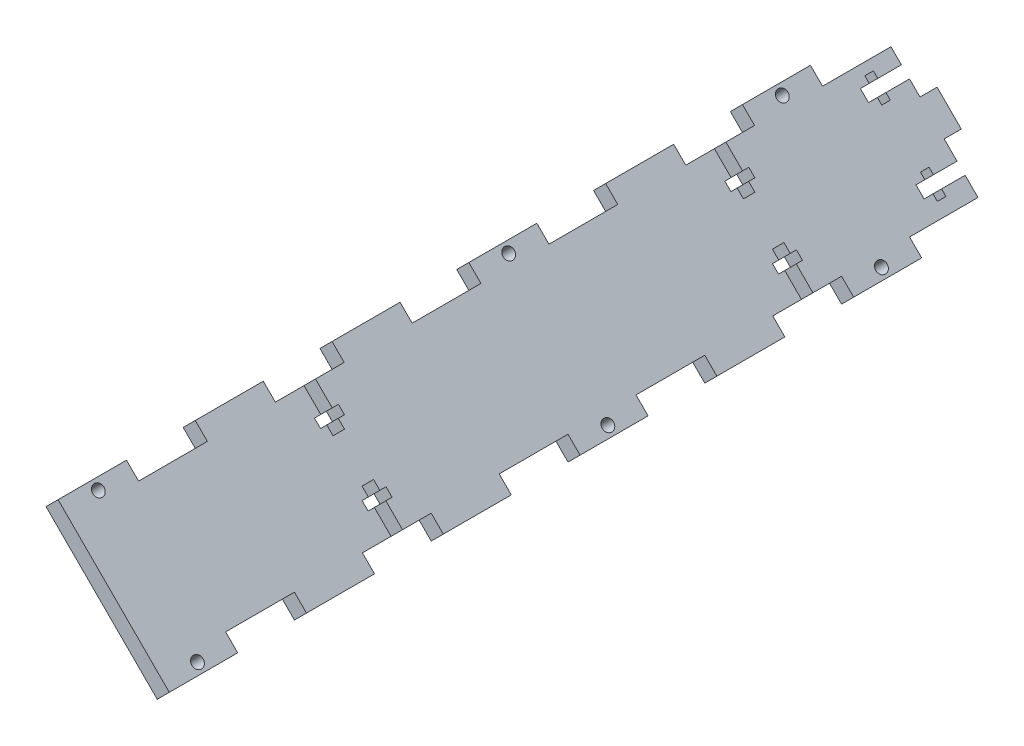
SolidWorks part; units mm, degrees
ref_plane "Front Plane" through (0, 0, 0) normal (0, 0, 1) x (1, 0, 0)
ref_plane "Top Plane" through (0, 0, 0) normal (0, 1, 0) x (1, 0, 0)
ref_plane "Right Plane" through (0, 0, 0) normal (1, 0, 0) x (0, 0, -1)
sketch "Sketch1" plane through (0, 0, 0) normal (0, 0, 1) x (1, 0, 0)
  line L0 (69.148, 48.095) -> (110.4572, 6.7859)
  line L1 (69.148, 48.095) -> (73.6381, 52.5852)
  line L2 (110.4572, 6.7859) -> (114.9473, 11.276)
  line L3 (73.6381, 52.5852) -> (114.9473, 11.276)
  line L4 (74.5361, -29.1352) -> (70.046, -24.645) construction
extrude "Boss-Extrude1" add sketch "Sketch1" along normal up to surface (304.8 mm away)
sketch "Sketch2" plane through (63.1116, 63.1116, 0) normal (0.7071, 0.7071, 0) x (0, 0, -1)
  line L0 (-304.8, -14.8867) -> (0, -14.8867) construction
  line L1 (-279.4, -21.2367) -> (-253.8574, -21.2367)
  line L2 (-279.4, -21.2367) -> (-279.4, -14.8867)
  line L3 (-279.4, -14.8867) -> (-253.8574, -14.8867)
  line L4 (-253.8574, -21.2367) -> (-253.8574, -14.8867)
  line L5 (-304.8, -73.3067) -> (0, -73.3067) construction
  line L6 (-279.4, -66.9567) -> (-253.8574, -66.9567)
  line L7 (-279.4, -66.9567) -> (-279.4, -73.3067)
  line L8 (-279.4, -73.3067) -> (-253.8574, -73.3067)
  line L9 (-253.8574, -66.9567) -> (-253.8574, -73.3067)
extrude "Cut-Extrude1" cut sketch "Sketch2" against normal blind 6.35
pattern_linear "LPattern1" count 6 spacing 50.8 along (0, 0, -1) of "Cut-Extrude1"
sketch "Sketch3" plane through (0, 0, 0) normal (0, 0, -1) x (-1, 0, 0)
  line L0 (-84.4262, 32.8169) -> (-93.4064, 23.8366)
  line L1 (-73.6381, 43.6049) -> (-105.967, 11.276) construction
  line L2 (-93.4064, 23.8366) -> (-97.8965, 28.3267)
  line L3 (-110.4572, 15.7661) -> (-78.1282, 48.095) construction
  line L4 (-97.8965, 28.3267) -> (-88.9163, 37.307)
  line L5 (-88.9163, 37.307) -> (-84.4262, 32.8169)
  dimension "D1" = 21.6066
  dimension "D2" = 12.7
extrude "Boss-Extrude2" add sketch "Sketch3" along normal blind 6.35
sketch "Sketch4" plane through (58.6215, 58.6215, 0) normal (-0.7071, -0.7071, 0) x (-0.7071, 0.7071, 0)
  line L0 (-28.865, -4.261) -> (-28.865, -30.7468) construction
  line L1 (-58.075, -4.261) -> (-58.075, -30.7468) construction
  line L2 (-66.9567, 0) -> (-66.9567, -25.4) construction
  line L3 (-49.1933, 6.35) -> (-49.1933, 0) construction
  line L4 (-36.4933, 6.35) -> (-36.4933, 0) construction
  line L5 (-21.2367, -25.4) -> (-21.2367, 0) construction
  line L6 (-49.1933, 0) -> (-66.9567, 0) construction
  line L7 (-21.2367, 0) -> (-36.4933, 0) construction
  line B0 (-55.9414, 0) -> (-60.2086, 0)
  line B1 (-60.2086, -11.938) -> (-62.52, -11.938)
  line B2 (-62.52, -11.938) -> (-62.52, -8.763)
  line B3 (-62.52, -8.763) -> (-60.2086, -8.763)
  line B4 (-60.2086, -8.763) -> (-60.2086, 0)
  line B5 (-60.2086, -11.938) -> (-60.2086, -15.24)
  line B6 (-60.2086, -15.24) -> (-55.9414, -15.24)
  line B7 (-55.9414, -11.938) -> (-55.9414, -15.24)
  line B8 (-55.9414, -8.763) -> (-55.9414, 0)
  line B9 (-53.63, -8.763) -> (-55.9414, -8.763)
  line B10 (-53.63, -11.938) -> (-53.63, -8.763)
  line B11 (-55.9414, -11.938) -> (-53.63, -11.938)
  line B12 (-26.7314, 0) -> (-30.9986, 0)
  line B13 (-30.9986, -11.938) -> (-33.31, -11.938)
  line B14 (-33.31, -11.938) -> (-33.31, -8.763)
  line B15 (-33.31, -8.763) -> (-30.9986, -8.763)
  line B16 (-30.9986, -8.763) -> (-30.9986, 0)
  line B17 (-30.9986, -11.938) -> (-30.9986, -15.24)
  line B18 (-30.9986, -15.24) -> (-26.7314, -15.24)
  line B19 (-26.7314, -11.938) -> (-26.7314, -15.24)
  line B20 (-26.7314, -8.763) -> (-26.7314, 0)
  line B21 (-24.42, -8.763) -> (-26.7314, -8.763)
  line B22 (-24.42, -11.938) -> (-24.42, -8.763)
  line B23 (-26.7314, -11.938) -> (-24.42, -11.938)
sketch_block_instance "TSlot-1"
sketch_block "TSlot" parameters "D1"=3.302, "D2"=3.175
sketch_block_instance "TSlot-2"
extrude "Cut-Extrude2" cut sketch "Sketch4" against normal through all
sketch "Sketch5" plane through (58.6215, 58.6215, 0) normal (-0.7071, -0.7071, 0) x (-0.7071, 0.7071, 0)
  line L0 (-14.8867, -289.9664) -> (-21.2367, -294.2336) construction
  line L1 (-14.8867, -304.8) -> (-14.8867, -279.4) construction
  line L2 (-21.2367, -289.9664) -> (-14.8867, -289.9664) construction
  line L3 (-21.2367, -289.9664) -> (-14.8867, -294.2336) construction
  line L4 (-21.2367, -294.2336) -> (-14.8867, -294.2336) construction
  line L5 (-21.2367, -137.5664) -> (-14.8867, -141.8336) construction
  line L6 (-14.8867, -152.2574) -> (-14.8867, -127) construction
  line L7 (-21.2367, -141.8336) -> (-14.8867, -141.8336) construction
  line L8 (-21.2367, -141.8336) -> (-14.8867, -137.5664) construction
  line L9 (-21.2367, -152.4) -> (-21.2367, -141.8336) construction
  line L10 (-21.2367, -137.5664) -> (-14.8867, -137.5664) construction
  line L11 (-21.2367, -40.2336) -> (-14.8867, -35.9664) construction
  line L12 (-14.8867, -50.6574) -> (-14.8867, -25.4) construction
  line L13 (-21.2367, -35.9664) -> (-14.8867, -35.9664) construction
  line L14 (-21.2367, -35.9664) -> (-14.8867, -40.2336) construction
  line L15 (-21.2367, -40.2336) -> (-14.8867, -40.2336) construction
  circle A0 centre (-18.0617, -38.1) radius 2.0955
  circle A1 centre (-18.0617, -139.7) radius 2.0955
  circle A2 centre (-18.0617, -292.1) radius 2.0955
  dimension "D1" = 4.191
extrude "Cut-Extrude3" cut sketch "Sketch5" against normal through all
ref_plane "Midplane" through (31.1811, -31.1811, 0) normal (0.7071, -0.7071, 0) x (0, 0, -1)
mirror "Mirror1" about plane through (31.1811, -31.1811, 0) normal (0.7071, -0.7071, 0) of "Cut-Extrude3"
sketch "Sketch6" plane through (58.6215, 58.6215, 0) normal (-0.7071, -0.7071, 0) x (-0.7071, 0.7071, 0)
  line L0 (0, -215.8287) -> (-47.8431, -215.8287) construction
  line L1 (32.2115, -63.4287) -> (-38.3785, -63.4287) construction
  line L2 (-21.2367, -50.6574) -> (-14.8867, -50.6574) construction
  line L3 (-14.8867, -76.2) -> (-21.2367, -76.2) construction
  line L4 (-21.2367, -203.0574) -> (-14.8867, -203.0574) construction
  line L5 (-14.8867, -228.6) -> (-21.2367, -228.6) construction
  line L6 (-21.2367, -76.2) -> (-21.2367, -50.6574) construction
  line L7 (-21.2367, -228.6) -> (-21.2367, -203.0574) construction
  line B0 (-21.2367, -65.5623) -> (-21.2367, -61.2951)
  line B1 (-33.1747, -61.2951) -> (-33.1747, -58.9837)
  line B2 (-33.1747, -58.9837) -> (-29.9997, -58.9837)
  line B3 (-29.9997, -58.9837) -> (-29.9997, -61.2951)
  line B4 (-29.9997, -61.2951) -> (-21.2367, -61.2951)
  line B5 (-33.1747, -61.2951) -> (-36.4767, -61.2951)
  line B6 (-36.4767, -61.2951) -> (-36.4767, -65.5623)
  line B7 (-33.1747, -65.5623) -> (-36.4767, -65.5623)
  line B8 (-29.9997, -65.5623) -> (-21.2367, -65.5623)
  line B9 (-29.9997, -67.8737) -> (-29.9997, -65.5623)
  line B10 (-33.1747, -67.8737) -> (-29.9997, -67.8737)
  line B11 (-33.1747, -65.5623) -> (-33.1747, -67.8737)
  line B12 (-21.2367, -217.9623) -> (-21.2367, -213.6951)
  line B13 (-33.1747, -213.6951) -> (-33.1747, -211.3837)
  line B14 (-33.1747, -211.3837) -> (-29.9997, -211.3837)
  line B15 (-29.9997, -211.3837) -> (-29.9997, -213.6951)
  line B16 (-29.9997, -213.6951) -> (-21.2367, -213.6951)
  line B17 (-33.1747, -213.6951) -> (-36.4767, -213.6951)
  line B18 (-36.4767, -213.6951) -> (-36.4767, -217.9623)
  line B19 (-33.1747, -217.9623) -> (-36.4767, -217.9623)
  line B20 (-29.9997, -217.9623) -> (-21.2367, -217.9623)
  line B21 (-29.9997, -220.2737) -> (-29.9997, -217.9623)
  line B22 (-33.1747, -220.2737) -> (-29.9997, -220.2737)
  line B23 (-33.1747, -217.9623) -> (-33.1747, -220.2737)
sketch_block_instance "TSlot-3"
sketch_block_instance "TSlot-4"
extrude "Cut-Extrude4" cut sketch "Sketch6" against normal through all
mirror "Mirror2" about plane through (31.1811, -31.1811, 0) normal (0.7071, -0.7071, 0) of "Cut-Extrude4"
